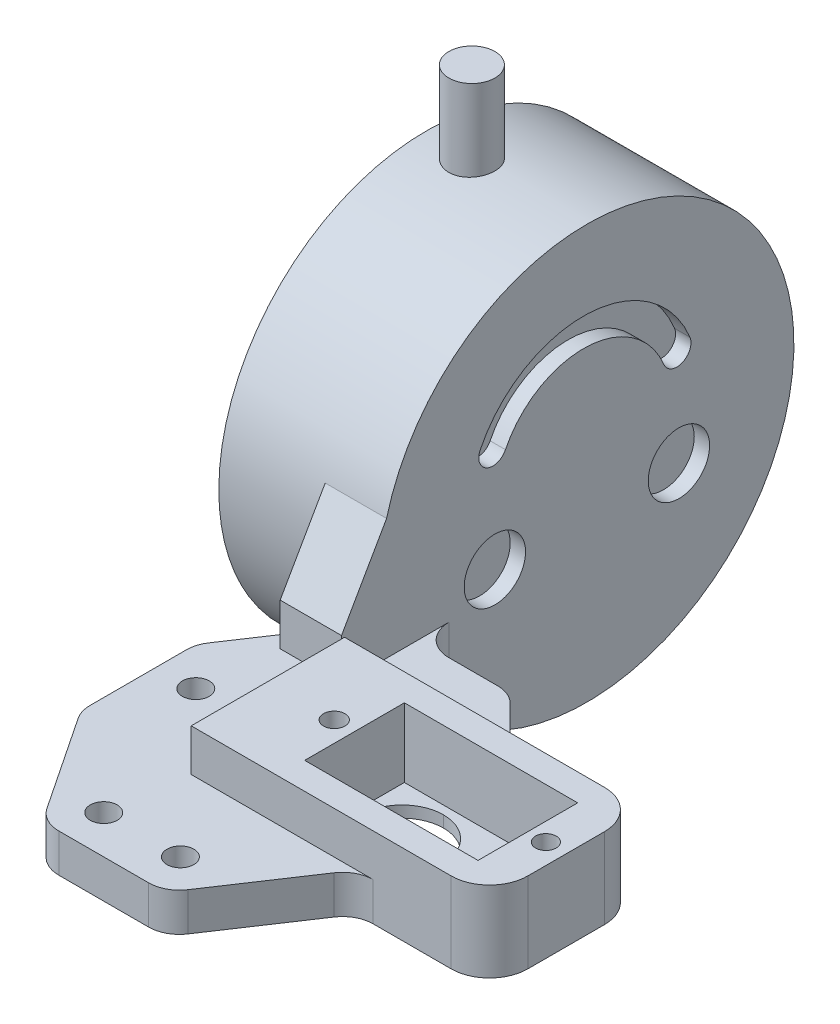
SolidWorks part; units mm, degrees
ref_plane "Front Plane" through (0, 0, 0) normal (0, 0, 1) x (1, 0, 0)
ref_plane "Top Plane" through (0, 0, 0) normal (0, 1, 0) x (1, 0, 0)
ref_plane "Right Plane" through (0, 0, 0) normal (1, 0, 0) x (0, 0, -1)
sketch "Sketch1" plane through (0, 0, 0) normal (0, 1, 0) x (1, 0, 0)
  line L0 (0, 0) -> (45, 0) construction
  line L1 (45, -10) -> (45, 10)
  line L2 (45, 10) -> (21, 10)
  line L3 (21, 10) -> (11.0015, 19.9985)
  line L4 (11.0015, 19.9985) -> (-4.9985, 19.9985)
  line L5 (-4.9985, 19.9985) -> (-14.9997, 4.9966)
  line L6 (-14.9997, 4.9966) -> (-14.9997, -10.0034)
  line L7 (-14.9997, -10.0034) -> (-4.9985, -25.0053)
  line L8 (-4.9985, -25.0053) -> (11.0015, -25.0053)
  line L9 (11.0015, -25.0053) -> (20.9977, -10)
  line L10 (20.9977, -10) -> (45, -10)
  point P5 (45, 0)
  dimension "D1" = 20
  dimension "D2" = 24
  dimension "D3" = 45
  dimension "D4" = 14.14
  dimension "D5" = 225
  dimension "D6" = 16
  dimension "D7" = 18.03
  dimension "D8" = 146.31
  dimension "D9" = 15
  dimension "D10" = 18.03
  dimension "D11" = 16
  dimension "D12" = 123.69
  dimension "D13" = 18.03
extrude "Boss-Extrude1" add sketch "Sketch1" along normal blind 5
sketch "Sketch2" plane through (0, 5, 0) normal (0, 1, 0) x (1, 0, 0)
  line L0 (45, 10) -> (45, 0) construction
  line L1 (45, -10) -> (45, 10) construction
  line L2 (45, 0) -> (-24.1028, 0) construction
  line L4 (-14.9997, 4.9966) -> (-14.9997, -10.0034) construction
  line L5 (-14.9997, -10.0034) -> (20.9977, -10) construction
  line L6 (2.999, -10.0017) -> (2.999, -20.0053) construction
  line L7 (-2.001, -20.0053) -> (7.999, -20.0053) construction
  line L8 (-4.9985, -25.0053) -> (11.0015, -25.0053) construction
  line L10 (11.5, -5.4) -> (22.3, -5.4)
  line L11 (11.5, -5.4) -> (11.5, 5.4)
  line L12 (11.5, 5.4) -> (22.3, 5.4)
  line L13 (22.3, -5.4) -> (22.3, 5.4)
  line L14 (11.5, -5.4) -> (22.3, 5.4) construction
  line L15 (11.5, 5.4) -> (22.3, -5.4) construction
  circle A0 centre (-9.9997, 0) radius 1.75
  circle A1 centre (-2.001, -20.0053) radius 1.75
  circle A2 centre (7.999, -20.0053) radius 1.75
  point P21 (2.999, -20.0053)
  point P25 (16.9, 0)
  dimension "D1" = 3.5
  dimension "D5" = 3.5
  dimension "D2" = 5
  dimension "D3" = 10
  dimension "D4" = 5
  dimension "D6" = 22.7
  dimension "D7" = 10.8
  dimension "D8" = 10.8
extrude "Cut-Extrude1" cut sketch "Sketch2" against normal through all
fillet "Fillet1" 2 edges at (11.5, 2.5, -5.4) (11.5, 2.5, 5.4) type full round first side face at (16.9, 2.5, -5.4) second side face at (16.9, 2.5, 5.4) middle face at (11.5, 2.5, 0)
fillet "Fillet2" 2 edges at (22.3, 2.5, -5.4) (22.3, 2.5, 5.4) type full round first side face at (19.6, 2.5, -5.4) second side face at (19.6, 2.5, 5.4) middle face at (22.3, 2.5, 0)
fillet "Fillet3" 2 edges at (45, 2.5, -10) (45, 2.5, 10) type full round first side face at (33, 2.5, -10) second side face at (32.9988, 2.5, 10) middle face at (45, 2.5, 0)
sketch "Sketch3" plane through (0, 5, 0) normal (0, 1, 0) x (1, 0, 0)
  line L0 (11.5, 0) -> (22.3, 0) construction
  line L1 (20.9977, -10) -> (35, -10) construction
  line L2 (5.4, 6.5) -> (28.4, 6.5)
  line L3 (5.4, 6.5) -> (5.4, -6.5)
  line L4 (5.4, -6.5) -> (28.4, -6.5)
  line L5 (28.4, 6.5) -> (28.4, -6.5)
  line L6 (5.4, 6.5) -> (28.4, -6.5) construction
  line L7 (5.4, -6.5) -> (28.4, 6.5) construction
  line L8 (-0.6, 10) -> (34.4, 10)
  line L9 (-0.6, 10) -> (-0.6, -10)
  line L10 (-0.6, -10) -> (34.4, -10)
  line L11 (34.4, 10) -> (34.4, -10)
  line L12 (-0.6, 10) -> (34.4, -10) construction
  line L13 (-0.6, -10) -> (34.4, 10) construction
  arc A0 (16.9, 5.4) -> (16.9, -5.4) centre (16.9, 0) ccw construction
  arc A1 (16.9, -5.4) -> (16.9, 5.4) centre (16.9, 0) ccw construction
  point P8 (16.9, 0)
  point P13 (16.9, 0)
  dimension "D1" = 6
  dimension "D2" = 13
  dimension "D3" = 23
extrude "Boss-Extrude2" add sketch "Sketch3" along normal blind 5.5
sketch "Sketch4" plane through (0, 5, 0) normal (0, 1, 0) x (1, 0, 0)
  line L4 (5.4, -6.5) -> (28.4, -6.5)
  line L5 (28.4, -6.5) -> (28.4, 6.5)
  line L6 (28.4, 6.5) -> (5.4, 6.5)
  line L7 (5.4, 6.5) -> (5.4, -6.5)
  line L8 (5.4, -6.5) -> (28.4, -6.5)
  line L9 (28.4, -6.5) -> (28.4, 6.5)
  line L10 (28.4, 6.5) -> (5.4, 6.5)
  line L11 (5.4, 6.5) -> (5.4, -6.5)
  dimension "D1" = 0
extrude "Cut-Extrude2" cut sketch "Sketch4" against normal blind 3.5
sketch "Sketch5" plane through (0, 5, 0) normal (0, 1, 0) x (1, 0, 0)
  line L3 (34.4, 10) -> (34.4, -10)
  line L4 (34.4, -10) -> (35, -10)
  line L5 (35, 10) -> (34.4, 10)
  line L6 (34.4, 10) -> (34.4, -10)
  line L7 (34.4, -10) -> (35, -10)
  line L8 (35, 10) -> (34.4, 10)
  arc A1 (35, -10) -> (35, 10) centre (35, 0) ccw
  arc A2 (35, -10) -> (35, 10) centre (35, 0) ccw
  dimension "D1" = 0
extrude "Cut-Extrude3" cut sketch "Sketch5" against normal through all body kept at (20.9977, 0, 10)
fillet "Fillet4" radius 4 2 edges at (34.4, 5.25, 10) (34.4, 5.25, -10)
sketch "Sketch6" plane through (0, 0, -19.9985) normal (0, 0, -1) x (-1, 0, 0)
  line L0 (-11.0015, 0) -> (4.9985, 0) construction
  line L1 (0.9985, 0) -> (8.9985, 0)
  line L2 (0.9985, 0) -> (0.9985, 28)
  line L3 (0.9985, 28) -> (8.9985, 28)
  line L4 (8.9985, 0) -> (8.9985, 28)
  line L5 (4.9985, 5) -> (4.9985, 0) construction
  dimension "D1" = 4
  dimension "D2" = 4
  dimension "D3" = 28
extrude "Boss-Extrude3" add sketch "Sketch6" along normal blind 32
fillet "Fillet5" radius 8 2 edges at (-4.9985, 0, -51.9985) (-4.9985, 28, -51.9985)
sketch "Sketch9" plane through (-8.9985, 0, 0) normal (-1, 0, 0) x (0, 0, 1)
  line L0 (-10, 10.5) -> (-19.9985, 28)
  line L1 (-19.9985, 28) -> (-19.9985, 0)
  line L2 (-19.9985, 0) -> (-10, 0)
  line L3 (-10, 0) -> (-10, 10.5)
extrude "Boss-Extrude6" add sketch "Sketch9" against normal up to surface (8 mm away) up to face at (-0.9985, 12.7143, -36.4719)
fillet "Fillet6" radius 4 9 edges at (20.9977, 2.5, 10) (21, 2.5, -10) (11.0015, 2.5, -19.9985) (-0.9985, 2.5, -19.9985) (-8.9985, 2.5, -13.9985) (-14.9997, 2.5, -4.9966) (-14.9997, 2.5, 10.0034) (-4.9985, 2.5, 25.0053) (11.0015, 2.5, 25.0053)
sketch "Sketch10" plane through (0, 1.5, 0) normal (0, 1, 0) x (1, 0, 0)
  line L0 (5.4, -6.5) -> (28.4, -6.5) construction
  line L1 (5.4, 6.5) -> (10.7, 6.5)
  line L2 (5.4, 6.5) -> (5.4, -6.5)
  line L3 (5.4, -6.5) -> (10.7, -6.5)
  line L4 (10.7, 6.5) -> (10.7, -6.5)
  line L5 (5.4, 0) -> (10.7, 0) construction
  circle A0 centre (8.05, 0) radius 1.4
  dimension "D2" = 2.8
  dimension "D1" = 5.3
extrude "Boss-Extrude7" add sketch "Sketch10" along normal up to surface (9 mm away) up to face at (21.6761, 10.5, 0)
sketch "Sketch11" plane through (0, 10.5, 0) normal (0, 1, 0) x (1, 0, 0)
  line L0 (30.4, 10) -> (38.3, 10)
  line L1 (38.3, 10) -> (38.3, -10)
  line L2 (38.3, -10) -> (30.4, -10)
  line L3 (34.4, -6) -> (34.4, 6) construction
  line L4 (34.4, -6) -> (34.4, 6)
  arc A0 (30.4, -10) -> (34.4, -6) centre (30.4, -6) ccw construction
  arc A1 (34.4, 6) -> (30.4, 10) centre (30.4, 6) ccw construction
  arc A2 (30.4, -10) -> (34.4, -6) centre (30.4, -6) ccw
  arc A3 (34.4, 6) -> (30.4, 10) centre (30.4, 6) ccw
  dimension "D1" = 7.9
extrude "Boss-Extrude8" add sketch "Sketch11" against normal up to surface (10.5 mm away) up to face at (6.82, 0, -3.7768)
sketch "Sketch12" plane through (0, 10.5, 0) normal (0, 1, 0) x (1, 0, 0)
  line L0 (8.05, 0) -> (35.65, 0) construction
  circle A0 centre (35.65, 0) radius 1.35
  dimension "D2" = 2.7
  dimension "D1" = 27.6
extrude "Cut-Extrude4" cut sketch "Sketch12" against normal up to surface (9 mm away) up to face at (8.05, 1.5, 1.4)
fillet "Fillet8" radius 5 2 edges at (38.3, 5.25, 10) (38.3, 5.25, -10)
sketch "Sketch13" plane through (0, 10.5, 0) normal (0, 1, 0) x (1, 0, 0)
  line L1 (28.4, 6.5) -> (33.3, 6.5)
  line L2 (28.4, 6.5) -> (28.4, -6.5)
  line L3 (28.4, -6.5) -> (33.3, -6.5)
  line L4 (33.3, 6.5) -> (33.3, -6.5)
  dimension "D1" = 4.9
extrude "Cut-Extrude5" cut sketch "Sketch13" against normal up to surface (9 mm away) up to face at (19.55, 1.5, 0)
sketch "Sketch14" plane through (-0.9985, 0, 0) normal (1, 0, 0) x (0, 0, -1)
  line L0 (41, 28) -> (41, 0) construction
  line L1 (43.9985, 28) -> (19.9985, 28) construction
  line L2 (43.9985, 0) -> (23.9985, 0) construction
  line L3 (51.9985, 14) -> (29.6413, 14) construction
  line L4 (51.9985, 20) -> (51.9985, 8) construction
  line L5 (10, 10.5) -> (10, 5) construction
  circle A0 centre (41, 22) radius 3
  circle A2 centre (41, 6) radius 3
  dimension "D1" = 6
  dimension "D2" = 16
  dimension "D3" = 31
extrude "Cut-Extrude6" cut sketch "Sketch14" against normal through all
fillet "Fillet10" radius 4 1 edges at (-4.9985, 28, -19.9985)
sketch "Sketch15" plane through (-8.9985, 0, 0) normal (-1, 0, 0) x (0, 0, 1)
  line L0 (-51.9985, 8) -> (-51.9985, 20) construction
  circle A0 centre (-41.9985, 13.9585) radius 27
  dimension "D1" = 54
  dimension "D2" = 10
extrude "Boss-Extrude9" add sketch "Sketch15" against normal up to surface (8 mm away) and the other way blind 13 up to face at (-0.9985, 22, -44)
ref_plane "Plane1" through (0, 13.9585, 0) normal (0, 1, 0) x (1, 0, 0)
sketch "Sketch17" plane through (0, 13.9585, 0) normal (0, 1, 0) x (1, 0, 0)
  line L0 (-21.9985, 68.9985) -> (-21.9985, 14.9985) construction
  line L2 (-21.9985, 41.9985) -> (3.5963, 41.9985) construction
  circle A0 centre (-15.9985, 41.9985) radius 3
  point P6 (-15.9985, 41.9985)
  dimension "D1" = 6
  dimension "D2" = 6
extrude "Boss-Extrude10" add sketch "Sketch17" along normal mid plane 75
sketch "Sketch18" plane through (-0.9985, 0, 0) normal (1, 0, 0) x (0, 0, -1)
  line L0 (33.1642, 13.9585) -> (-33.1642, 13.9585) construction
  line L1 (41.9985, 13.9585) -> (41.9985, -13.0415) construction
  line L2 (23.9985, 5) -> (23.9985, 0) construction
  line L3 (23.9985, 0) -> (18.8866, 0) construction
  circle A0 centre (53.9985, 7.9585) radius 4
  circle A1 centre (29.9985, 7.9585) radius 4
  arc A2 (53.7329, 20.7875) -> (29.7329, 21.6087) centre (41.5482, 15.8004) ccw construction
  arc A3 (18.8866, 0) -> (15.8753, 20.7833) centre (41.9985, 13.9585) ccw construction
  arc A4 (55.4305, 21.4822) -> (28.0869, 22.4179) centre (41.5482, 15.8004) ccw
  arc A5 (52.0354, 20.0927) -> (31.379, 20.7995) centre (41.5482, 15.8004) ccw
  arc A6 (52.0354, 20.0927) -> (55.4305, 21.4822) centre (53.7329, 20.7875) ccw
  arc A7 (28.0869, 22.4179) -> (31.379, 20.7995) centre (29.7329, 21.6087) ccw
  point P14 (41.9985, 28.9585)
  point P19 (0, 0)
  point P20 (0, 0)
  point P21 (0, 0)
  point P22 (0, 0)
  point P23 (0, 0)
  point P24 (0, 0)
  point P25 (29.7329, 3.9585)
  dimension "D1" = 8
  dimension "D2" = 8
  dimension "D6" = 15
  dimension "D8" = 11.3316
  dimension "D9" = 7.3805
  dimension "D3" = 6
  dimension "D4" = 12
  dimension "D5" = 12
  dimension "D7" = 15
  dimension "D10" = 17.5497
extrude "Cut-Extrude7" cut sketch "Sketch18" against normal blind 2
